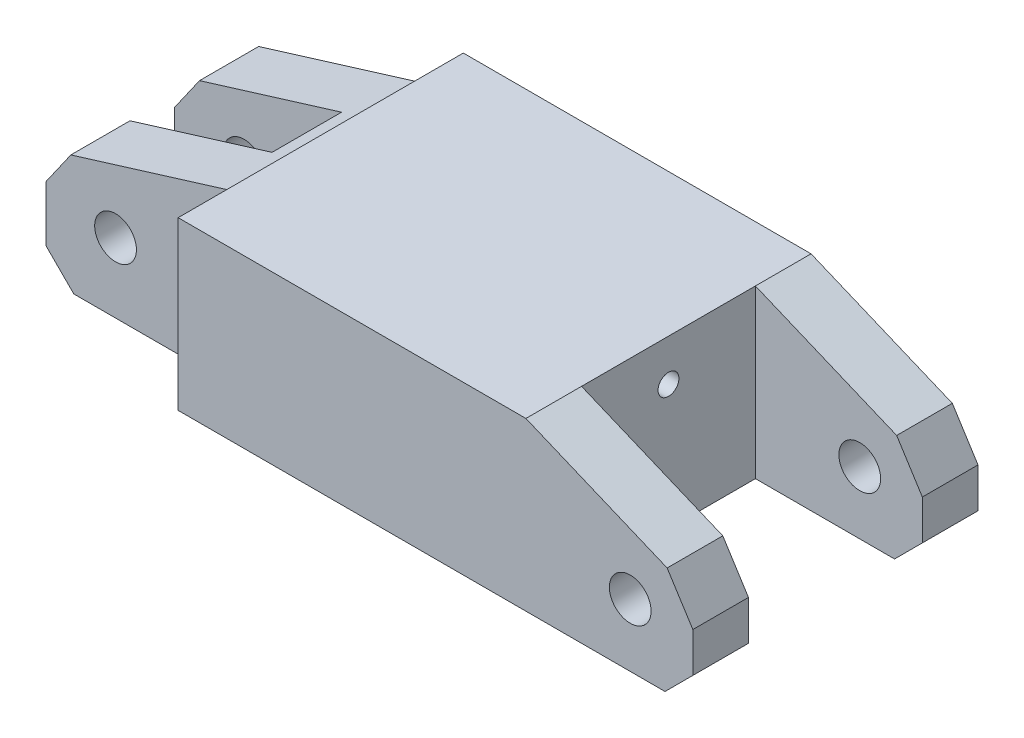
SolidWorks part; units mm, degrees
ref_plane "Спереди" through (0, 0, 0) normal (0, 0, 1) x (1, 0, 0)
ref_plane "Сверху" through (0, 0, 0) normal (0, 1, 0) x (1, 0, 0)
ref_plane "Справа" through (0, 0, 0) normal (1, 0, 0) x (0, 0, -1)
sketch "Эскиз2" plane through (0, 0, 0) normal (1, 0, 0) x (0, 0, -1)
  line L1 (-10.25, 6) -> (10.25, 6)
  line L2 (-10.25, 6) -> (-10.25, -6)
  line L3 (-10.25, -6) -> (10.25, -6)
  line L4 (10.25, 6) -> (10.25, -6)
  line L5 (-10.25, 6) -> (10.25, -6) construction
  line L6 (-10.25, -6) -> (10.25, 6) construction
  point P0 (0, 0)
extrude "Вытянуть1" add sketch "Эскиз2" along normal blind 50
sketch "Эскиз3" plane through (0, 6, 0) normal (0, 1, 0) x (1, 0, 0)
  line L0 (0, 0) -> (-9.2006, 0) construction
  line L1 (0, 10.25) -> (0, -10.25) construction
  line L2 (-12, 2.5) -> (12, 2.5)
  line L3 (-12, 2.5) -> (-12, -2.5)
  line L4 (-12, -2.5) -> (12, -2.5)
  line L5 (12, 2.5) -> (12, -2.5)
  line L6 (-12, 2.5) -> (12, -2.5) construction
  line L7 (-12, -2.5) -> (12, 2.5) construction
  point P1 (0, 0)
  dimension "D1" = 12
extrude "Вырез-Вытянуть1" cut sketch "Эскиз3" against normal through all
sketch "Эскиз5" plane through (0, 6, 0) normal (0, 1, 0) x (1, 0, 0)
  line L0 (40, 0) -> (51.6105, 0) construction
  line L1 (50, 10.25) -> (0, 10.25) construction
  line L2 (50, 10.25) -> (50, -10.25) construction
  line L3 (38, 6.25) -> (51.1226, 6.25)
  line L4 (38, 6.25) -> (38, -6.25)
  line L5 (38, -6.25) -> (51.1226, -6.25)
  line L6 (51.1226, 6.25) -> (51.1226, -6.25)
  line L7 (38, 6.25) -> (51.1226, -6.25) construction
  line L8 (38, -6.25) -> (51.1226, 6.25) construction
  point P1 (44.5613, 0)
  dimension "D1" = 12
  dimension "D2" = 4
extrude "Вырез-Вытянуть2" cut sketch "Эскиз5" against normal through all
sketch "Эскиз7" plane through (38, 0, 0) normal (1, 0, 0) x (0, 0, -1)
  line L0 (0, 6) -> (0, 3.9395) construction
  line L1 (6.25, 6) -> (-6.25, 6) construction
  circle A0 centre (0, 3) radius 0.75
  dimension "D1" = 3
extrude "Вытянуть3" cut sketch "Эскиз7" against normal through all
sketch "Эскиз10" plane through (0, 6, 0) normal (0, 1, 0) x (1, 0, 0)
  line L0 (5.6157, 0) -> (-3.5713, 0) construction
  line L1 (0, 10.25) -> (0, 2.5) construction
  line L2 (12, 2.5) -> (0, 2.5) construction
  line L3 (-6.1065, 15.4507) -> (13, 15.4507)
  line L4 (-6.1065, 15.4507) -> (-6.1065, 6.75)
  line L5 (-6.1065, 6.75) -> (13, 6.75)
  line L6 (13, 15.4507) -> (13, 6.75)
  line L7 (-6.1065, -15.4507) -> (13, -15.4507)
  line L8 (-6.1065, -15.4507) -> (-6.1065, -6.75)
  line L9 (-6.1065, -6.75) -> (13, -6.75)
  line L10 (13, -15.4507) -> (13, -6.75)
  dimension "D1" = 4.25
  dimension "D2" = 13
extrude "Вырез-Вытянуть3" cut sketch "Эскиз10" against normal through all
sketch "Эскиз11" plane through (0, 0, 6.75) normal (0, 0, 1) x (1, 0, 0)
  line L0 (0, -6) -> (0, 6) construction
  line L2 (13, -6) -> (0, -6) construction
  circle A0 centre (5, -1) radius 1.5
  dimension "D1" = 5
  dimension "D2" = 5
extrude "Вытянуть6" cut sketch "Эскиз11" against normal through all
sketch "Эскиз9" plane through (0, 0, 10.25) normal (0, 0, 1) x (1, 0, 0)
  line L0 (50, 6) -> (50, -6) construction
  line L2 (50, -6) -> (13, -6) construction
  circle A0 centre (45.5, -1.5) radius 1.5
  dimension "D1" = 4.5
  dimension "D2" = 4.5
extrude "Вытянуть5" cut sketch "Эскиз9" against normal through all
sketch "Эскиз12" plane through (12, 0, 0) normal (-1, 0, 0) x (0, 0, 1)
  circle A0 centre (-1.7914, -3.4073) radius 0.75
extrude "Вырез-Вытянуть4" cut sketch "Эскиз12" against normal blind 12
sketch "Эскиз13" plane through (0, 0, 10.25) normal (0, 0, 1) x (1, 0, 0)
  line L0 (13, 6) -> (0, 6)
  line L1 (50, 6) -> (13, 6) construction
  line L2 (0, -6) -> (0, 6) construction
  line L3 (0, 6) -> (0, 2)
  line L4 (0, 2) -> (13, 6)
  line L6 (50, 6) -> (50, 1)
  line L7 (13, 6) -> (0, 6) construction
  line L8 (50, 1) -> (38, 6)
  line L9 (38, 6) -> (50, 6)
  line L10 (50, 6) -> (50, -6) construction
  dimension "D2" = 4
  dimension "D1" = 13
  dimension "D3" = 12
extrude "Вытянуть7" cut sketch "Эскиз13" against normal through all
chamfer "Фаска5" distance 2 angle 45 4 edges at (0, -6, 4.625) (0, -6, -4.625) (50, -6, -8.25) (50, -6, 8.25)
chamfer "Фаска6" distance 2 angle 35 4 edges at (0, 2, 4.625) (0, 2, -4.625) (50, 1, -8.25) (50, 1, 8.25) first distance on face at (0, -1, 4.625) first distance on face at (0, -1, -4.625) first distance on face at (44, 3.5, -8.25) first distance on face at (44, 3.5, 8.25)
sketch "Эскиз14" plane through (38, 0, 0) normal (1, 0, 0) x (0, 0, -1)
  line L0 (-6.25, -1.1421) -> (-6.25, -4) construction
  line L1 (6.25, -6) -> (-6.25, -6) construction
  circle A0 centre (-2, -3.75) radius 0.75
  dimension "D1" = 4.25
  dimension "D2" = 2.25
extrude "Вырез-Вытянуть5" cut sketch "Эскиз14" against normal blind 6
sketch "Эскиз15" plane through (0, -6, 0) normal (0, -1, 0) x (1, 0, 0)
  line L0 (13, 10.25) -> (13, 6.75) construction
  line L1 (18, 6.25) -> (32, 6.25)
  line L2 (15, 3.25) -> (15, -3.25)
  line L3 (18, -6.25) -> (32, -6.25)
  line L4 (35, 3.25) -> (35, -3.25)
  line L5 (38, -6.25) -> (38, 6.25) construction
  line L6 (48, 10.25) -> (13, 10.25) construction
  line L7 (48, -10.25) -> (13, -10.25) construction
  arc A0 (18, 6.25) -> (15, 3.25) centre (18, 3.25) ccw
  arc A1 (35, 3.25) -> (32, 6.25) centre (32, 3.25) ccw
  arc A2 (32, -6.25) -> (35, -3.25) centre (32, -3.25) ccw
  arc A3 (15, -3.25) -> (18, -6.25) centre (18, -3.25) ccw
  dimension "D5" = 3
  dimension "D1" = 2
  dimension "D2" = 3
  dimension "D3" = 4
  dimension "D4" = 4
extrude "Вытянуть8" cut sketch "Эскиз15" against normal blind 10
sketch "Эскиз16" plane through (12, 0, 0) normal (-1, 0, 0) x (0, 0, 1)
  circle A0 centre (1.7484, 3.0009) radius 0.75
extrude "Вытянуть9" cut sketch "Эскиз16" against normal blind 5
